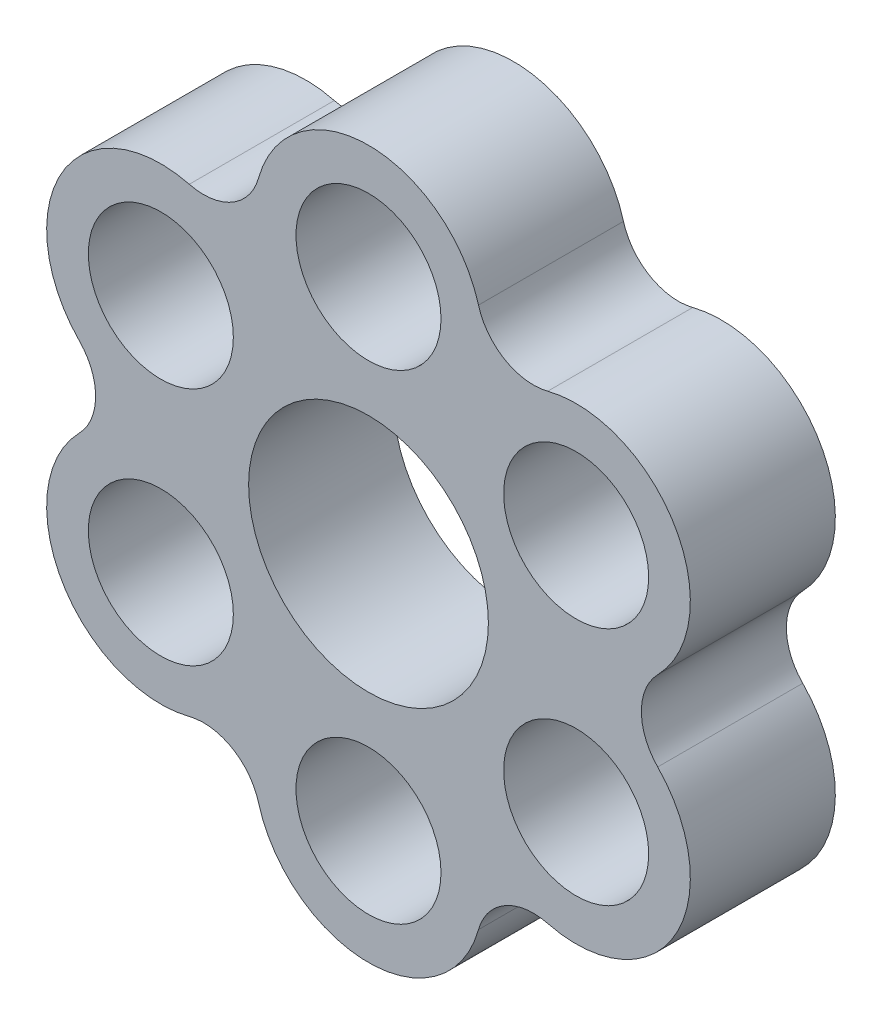
SolidWorks part; units mm, degrees
material "6061-T6 (SS)"
ref_plane "Front Plane" through (0, 0, 0) normal (0, 0, 1) x (1, 0, 0)
ref_plane "Top Plane" through (0, 0, 0) normal (0, 1, 0) x (1, 0, 0)
ref_plane "Right Plane" through (0, 0, 0) normal (1, 0, 0) x (0, 0, -1)
sketch "Sketch1" plane through (0, 0, 0) normal (0, 0, 1) x (1, 0, 0)
  circle A0 centre (0, 0) radius 45 construction
  circle A1 centre (0, 0) radius 37.5 construction
  circle A2 centre (0, 0) radius 10.5
  arc A3 (9.6329, 23.6847) -> (-9.6329, 23.6847) centre (0, 21) ccw
  arc A4 (25.328, 3.5) -> (15.6951, 20.1847) centre (18.1865, 10.5) ccw
  arc A5 (15.6951, -20.1847) -> (25.328, -3.5) centre (18.1865, -10.5) ccw
  arc A6 (-9.6329, -23.6847) -> (9.6329, -23.6847) centre (0, -21) ccw
  arc A7 (-25.328, -3.5) -> (-15.6951, -20.1847) centre (-18.1865, -10.5) ccw
  arc A8 (-15.6951, 20.1847) -> (-25.328, 3.5) centre (-18.1865, 10.5) ccw
  arc A9 (-15.6951, 20.1847) -> (-9.6329, 23.6847) centre (-14.4493, 25.027) ccw
  arc A10 (9.6329, 23.6847) -> (15.6951, 20.1847) centre (14.4493, 25.027) ccw
  arc A11 (25.328, 3.5) -> (25.328, -3.5) centre (28.8987, 0) ccw
  arc A12 (15.6951, -20.1847) -> (9.6329, -23.6847) centre (14.4493, -25.027) ccw
  arc A13 (-9.6329, -23.6847) -> (-15.6951, -20.1847) centre (-14.4493, -25.027) ccw
  arc A14 (-25.328, -3.5) -> (-25.328, 3.5) centre (-28.8987, 0) ccw
  arc A15 (-25.328, 3.5) -> (-15.6951, 20.1847) centre (-18.1865, 10.5) ccw construction
  arc A16 (-9.6329, 23.6847) -> (9.6329, 23.6847) centre (0, 21) ccw construction
  arc A17 (15.6951, 20.1847) -> (25.328, 3.5) centre (18.1865, 10.5) ccw construction
  arc A18 (25.328, -3.5) -> (15.6951, -20.1847) centre (18.1865, -10.5) ccw construction
  arc A19 (9.6329, -23.6847) -> (-9.6329, -23.6847) centre (0, -21) ccw construction
  arc A20 (-15.6951, -20.1847) -> (-25.328, -3.5) centre (-18.1865, -10.5) ccw construction
  circle A21 centre (0, 21) radius 6.35
  circle A22 centre (18.1865, 10.5) radius 6.35
  circle A23 centre (18.1865, -10.5) radius 6.35
  circle A24 centre (0, -21) radius 6.35
  circle A25 centre (-18.1865, -10.5) radius 6.35
  circle A26 centre (-18.1865, 10.5) radius 6.35
  point P19 (0, 0)
  point P38 (0, 0)
  point P44 (0, 0)
  dimension "D1" = 90
  dimension "D2" = 75
  dimension "D3" = 21
  dimension "D4" = 20
  dimension "D7" = 5
  dimension "D9" = 12.7
  dimension "D5" = 21
  dimension "D6" = 6
  dimension "D8" = 6
  dimension "D10" = 6
extrude "Boss-Extrude1" add sketch "Sketch1" along normal mid plane 12.7
equation "\"D9@Sketch1\"=0.5in"
equation "\"D1@Boss-Extrude1\"=0.5in"
